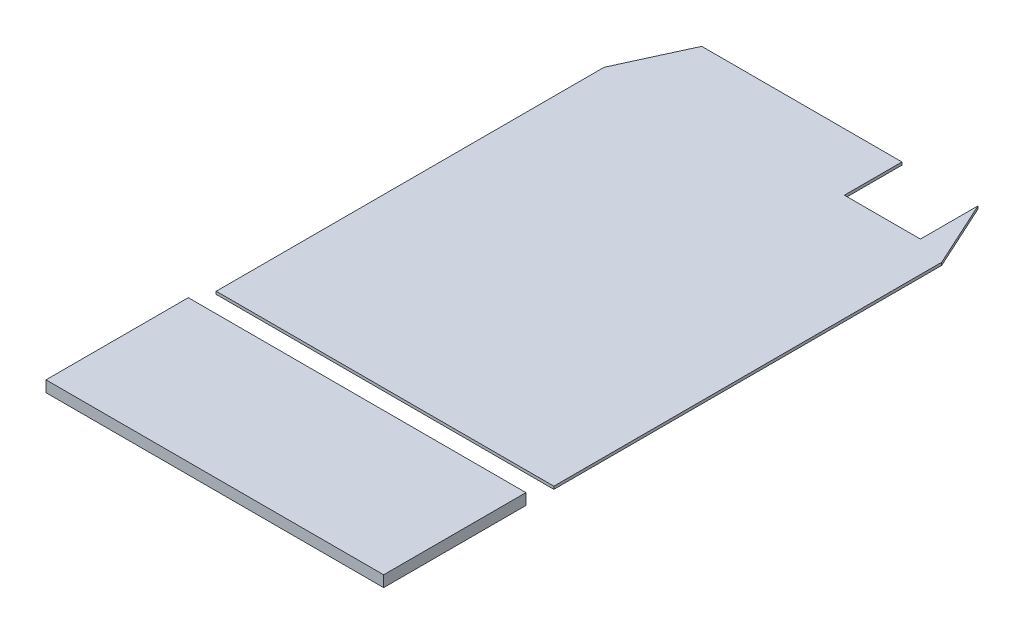
SolidWorks part; units mm, degrees
ref_plane "Front Plane" through (0, 0, 0) normal (0, 0, 1) x (1, 0, 0)
ref_plane "Top Plane" through (0, 0, 0) normal (0, 1, 0) x (1, 0, 0)
ref_plane "Right Plane" through (0, 0, 0) normal (1, 0, 0) x (0, 0, -1)
sketch "Sketch1" plane through (0, 0, 0) normal (0, 1, 0) x (1, 0, 0)
  line L0 (-96.0438, 177.8) -> (35.3219, 177.8)
  line L1 (96.0438, -177.8) -> (-96.0438, -177.8)
  line L2 (96.0438, -177.8) -> (96.0437, 177.8)
  line L4 (-96.0438, -177.8) -> (-96.0438, 177.8)
  line L5 (96.0438, -177.8) -> (-96.0438, 177.8) construction
  line L6 (96.0437, 177.8) -> (-96.0438, -177.8) construction
  line L7 (35.3219, 177.8) -> (35.3219, 145.0362)
  line L8 (35.3219, 145.0362) -> (78.5812, 145.0362)
  line L9 (78.5812, 145.0362) -> (78.5812, 177.8)
  line L10 (78.5812, 177.8) -> (96.0437, 177.8)
  point P0 (0, 0)
  dimension "D1" = 355.6
  dimension "D2" = 192.0875
  dimension "D3" = 43.2594
  dimension "D4" = 17.4625
extrude "Boss-Extrude1" add sketch "Sketch1" along normal blind 1.5875 contours L4 L0 L7 L8 L9 L10 L2 L1
sketch "Sketch2" plane through (0, 1.5875, 0) normal (0, 1, 0) x (1, 0, 0)
  line L0 (96.0438, -177.8) -> (96.0437, 177.8) construction
  line L1 (96.0438, -80.9625) -> (-96.0437, -80.9625)
  line L2 (96.0438, -80.9625) -> (96.0438, -96.8375)
  line L3 (96.0438, -96.8375) -> (-96.0438, -96.8375)
  line L4 (-96.0437, -80.9625) -> (-96.0438, -96.8375)
  line L5 (-96.0438, -177.8) -> (-96.0438, 177.8) construction
  line L6 (-78.5813, 177.8) -> (-96.0438, 139.7)
  line L7 (-96.0438, 177.8) -> (35.3219, 177.8) construction
  line L8 (-96.0438, 139.7) -> (-96.0438, 177.8)
  line L9 (-96.0438, 177.8) -> (-78.5813, 177.8)
  line L13 (96.0438, -177.8) -> (-96.0438, -177.8) construction
  line L14 (96.0437, 139.7) -> (78.5812, 177.8)
  line L15 (78.5812, 177.8) -> (96.0437, 177.8) construction
  line L16 (78.5812, 177.8) -> (96.0437, 177.8)
  line L17 (96.0437, 177.8) -> (96.0437, 139.7)
  point P22 (78.5812, 177.8)
  dimension "D1" = 15.875
  dimension "D2" = 80.9625
  dimension "D3" = 38.1
extrude "Cut-Extrude1" cut sketch "Sketch2" against normal up to surface (1.5875 mm away) up to face at (28.4758, 0, -80.709)
sketch "Sketch3" plane through (0, 1.5875, 0) normal (0, 1, 0) x (1, 0, 0)
  line L1 (-96.0438, -96.8375) -> (96.0438, -96.8375)
  line L2 (-96.0438, -96.8375) -> (-96.0438, -177.8)
  line L3 (-96.0438, -177.8) -> (96.0438, -177.8)
  line L4 (96.0438, -96.8375) -> (96.0438, -177.8)
extrude "Boss-Extrude2" add sketch "Sketch3" along normal blind 4.7625
